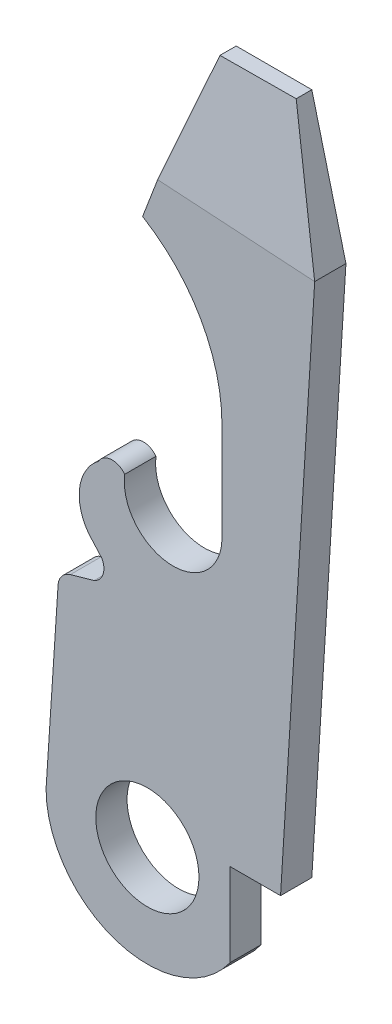
SolidWorks part; units mm, degrees
ref_plane "Front Plane" through (0, 0, 0) normal (0, 0, 1) x (1, 0, 0)
ref_plane "Top Plane" through (0, 0, 0) normal (0, 1, 0) x (1, 0, 0)
ref_plane "Right Plane" through (0, 0, 0) normal (1, 0, 0) x (0, 0, -1)
sketch "Sketch1" plane through (0, 0, 0) normal (0, 0, 1) x (1, 0, 0)
  line L0 (14.7211, 33.1224) -> (73.6054, 33.1224) construction
  line L1 (48.5741, 39.9438) -> (47.1882, 17.6494)
  line L2 (47.1882, 17.6494) -> (45.1335, 17.6494)
  line L3 (44.1152, 45.3668) -> (47.1882, 45.3668)
  line L4 (47.1882, 45.3668) -> (48.5741, 39.9438)
  line L5 (44.1152, 45.3668) -> (41.5845, 38.7387)
  line L6 (44.8079, 33.0413) -> (44.8079, 28.9774)
  line L7 (45.1335, 17.6494) -> (45.1335, 14.2643)
  line L8 (38.1481, 24.0097) -> (37.6632, 16.6481)
  line L9 (38.6472, 24.6724) -> (39.6181, 24.9516)
  line L10 (39.3816, 26.5076) -> (39.9317, 25.8857)
  arc A1 (40.8585, 29.3071) -> (44.8079, 28.9774) centre (42.8251, 29.0448) ccw
  arc A2 (39.787, 29.2265) -> (39.3816, 26.5076) centre (40.9821, 27.6586) ccw
  arc A3 (40.8585, 29.3071) -> (39.787, 29.2265) centre (40.3492, 28.9157) ccw
  arc A4 (39.6181, 24.9516) -> (39.9317, 25.8857) centre (39.3399, 25.5647) ccw
  arc A5 (38.6472, 24.6724) -> (38.1481, 24.0097) centre (38.8377, 24.0097) ccw
  arc A6 (37.6632, 16.6481) -> (45.1335, 14.2643) centre (41.7787, 16.6481) ccw
  arc A7 (44.8079, 33.0413) -> (41.5845, 38.7387) centre (38.1611, 33.0413) ccw
  dimension "D6" = 6.6468
  dimension "D7" = 1.984
  dimension "D8" = 1.9714
  dimension "D9" = 0.6733
  dimension "D10" = 4.1155
  dimension "D1" = 9.525
  dimension "D2" = 28.7187
  dimension "D3" = 3.073
  dimension "D4" = 110.898
  dimension "D5" = 104.335
extrude "Boss-Extrude1" add sketch "Sketch1" along normal blind 1.27
sketch "Sketch2" plane through (0, 0, 1.27) normal (0, 0, 1) x (1, 0, 0)
  circle A0 centre (41.7787, 16.6481) radius 2.0955
  dimension "D1" = 4.191
extrude "Cut-Extrude1" cut sketch "Sketch2" against normal through all
sketch "Sketch3" plane through (45.9137, -2.8541, 0) normal (0.9981, -0.062, 0) x (0, 0, -1)
  line L2 (-0.635, 48.2071) -> (-1.27, 42.8805)
  line L3 (-1.27, 42.8805) -> (-1.27, 48.2071)
  line L4 (-1.27, 48.2071) -> (-0.635, 48.2071)
  dimension "D1" = 0.635
extrude "Cut-Extrude2" cut sketch "Sketch3" against normal through all
